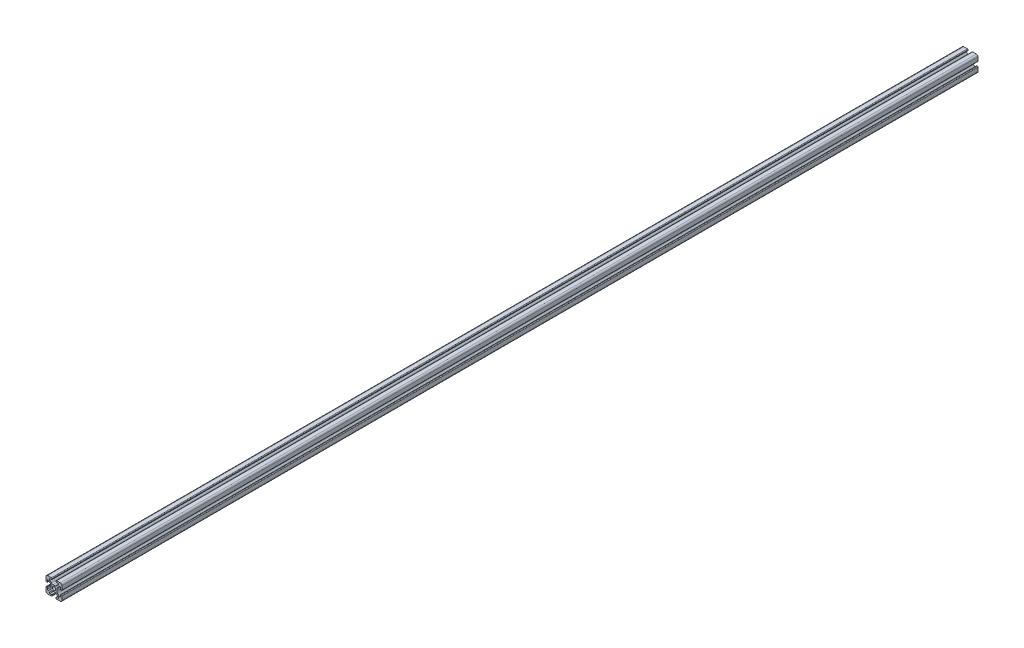
SolidWorks part; units mm, degrees
ref_plane "Front Plane" through (0, 0, 0) normal (0, 0, 1) x (1, 0, 0)
ref_plane "Top Plane" through (0, 0, 0) normal (0, 1, 0) x (1, 0, 0)
ref_plane "Right Plane" through (0, 0, 0) normal (1, 0, 0) x (0, 0, -1)
sketch "Sketch1" plane through (0, 0, 0) normal (0, 0, 1) x (1, 0, 0)
  line L0 (0, 10) -> (0, -10) construction
  line L1 (10, 0) -> (-10, 0) construction
  line L2 (-2.5, 10) -> (2.5, 10) construction
  line L3 (-5.75, 8.2) -> (5.75, 8.2) construction
  circle A0 centre (0, 0) radius 2.15 construction
  point P4 (0, 0)
  point P8 (0, 0)
  point P10 (0, 3.6)
  point P14 (0, 10)
  point P17 (0, 8.2)
  dimension "Thru Hole" = 4.3
  dimension "Height" = 20
  dimension "T Slot Depth" = 6.4
  dimension "T Slot Top Width" = 5
  dimension "T Slot Max Width" = 11.5
  dimension "Wall" = 1.8
sketch "Sketch2" plane through (0, 0, 0) normal (1, 0, 0) x (0, 0, -1)
  line L0 (575, 0) -> (-575, 0) construction
  point P4 (0, 0)
  dimension "D1" = 1150
sketch "Sketch3" plane through (0, 0, 0) normal (0, 0, 1) x (1, 0, 0)
  line L0 (3.2874, 10) -> (8, 10)
  line L1 (10, 8) -> (10, -8) construction
  line L2 (8, -10) -> (-8, -10) construction
  line L3 (-10, 10) -> (10, -10) construction
  line L4 (2.5, 9.2126) -> (2.5, 8.5048)
  line L5 (-5.75, 8.2) -> (5.75, 8.2) construction
  line L6 (2.8048, 8.2) -> (4.9118, 8.2)
  line L7 (5.5045, 6.7691) -> (3.2141, 4.4787)
  line L8 (1.0928, 3.6) -> (-1.0928, 3.6)
  line L9 (0, 10) -> (0, -10) construction
  line L10 (5.75, 8.2) -> (5.75, 0) construction
  line L11 (10, 0) -> (-10, 0) construction
  line L12 (0, 0) -> (0, 10) construction
  line L13 (-2.5, 9.2126) -> (-2.5, 8.5048)
  line L14 (-5.5045, 6.7691) -> (-3.2141, 4.4787)
  line L15 (-2.8048, 8.2) -> (-4.9118, 8.2)
  line L16 (-3.2874, 10) -> (-8, 10)
  line L17 (0, 0) -> (-10, 0) construction
  line L18 (-10, 3.2874) -> (-10, 8)
  line L19 (-8.2, 2.8048) -> (-8.2, 4.9118)
  line L20 (-6.7691, 5.5045) -> (-4.4787, 3.2141)
  line L21 (-9.2126, 2.5) -> (-8.5048, 2.5)
  line L22 (-3.6, -1.0928) -> (-3.6, 1.0928)
  line L23 (-6.7691, -5.5045) -> (-4.4787, -3.2141)
  line L24 (-8.2, -2.8048) -> (-8.2, -4.9118)
  line L25 (-9.2126, -2.5) -> (-8.5048, -2.5)
  line L26 (-10, -3.2874) -> (-10, -8)
  line L27 (9.2126, -2.5) -> (8.5048, -2.5)
  line L28 (8.2, -2.8048) -> (8.2, -4.9118)
  line L29 (6.7691, -5.5045) -> (4.4787, -3.2141)
  line L30 (3.6, -1.0928) -> (3.6, 1.0928)
  line L31 (9.2126, 2.5) -> (8.5048, 2.5)
  line L32 (6.7691, 5.5045) -> (4.4787, 3.2141)
  line L33 (8.2, 2.8048) -> (8.2, 4.9118)
  line L34 (10, 8) -> (10, 3.2874)
  line L35 (10, -3.2874) -> (10, -8)
  line L36 (3.2874, -10) -> (8, -10)
  line L37 (-3.2874, -10) -> (-8, -10)
  line L38 (-6.7691, -5.5045) -> (-4.4787, -3.2141)
  line L39 (-2.8048, -8.2) -> (-4.9118, -8.2)
  line L40 (-5.5045, -6.7691) -> (-3.2141, -4.4787)
  line L41 (-2.5, -9.2126) -> (-2.5, -8.5048)
  line L42 (1.0928, -3.6) -> (-1.0928, -3.6)
  line L43 (5.5045, -6.7691) -> (3.2141, -4.4787)
  line L44 (2.8048, -8.2) -> (4.9118, -8.2)
  line L45 (2.5, -9.2126) -> (2.5, -8.5048)
  arc A0 (4.9118, 8.2) -> (5.5045, 6.7691) centre (4.9118, 7.3618) cw
  arc A1 (3.2141, 4.4787) -> (1.0928, 3.6) centre (1.0928, 6.6) cw
  circle A2 centre (0, 0) radius 2.15 construction
  circle A3 centre (0, 0) radius 2.15
  arc A4 (3.2874, 10) -> (2.5, 9.2126) centre (3.2874, 9.2126) ccw
  arc A5 (2.5, 8.5048) -> (2.8048, 8.2) centre (2.8048, 8.5048) ccw
  arc A6 (-3.2874, 10) -> (-2.5, 9.2126) centre (-3.2874, 9.2126) cw
  arc A7 (-4.9118, 8.2) -> (-5.5045, 6.7691) centre (-4.9118, 7.3618) ccw
  arc A8 (-3.2141, 4.4787) -> (-1.0928, 3.6) centre (-1.0928, 6.6) ccw
  arc A9 (-2.5, 8.5048) -> (-2.8048, 8.2) centre (-2.8048, 8.5048) cw
  arc A10 (-8.5048, 2.5) -> (-8.2, 2.8048) centre (-8.5048, 2.8048) ccw
  arc A11 (-4.4787, 3.2141) -> (-3.6, 1.0928) centre (-6.6, 1.0928) cw
  arc A12 (-8.2, 4.9118) -> (-6.7691, 5.5045) centre (-7.3618, 4.9118) cw
  arc A13 (-10, 3.2874) -> (-9.2126, 2.5) centre (-9.2126, 3.2874) ccw
  arc A14 (-8.5048, -2.5) -> (-8.2, -2.8048) centre (-8.5048, -2.8048) cw
  arc A15 (-10, -3.2874) -> (-9.2126, -2.5) centre (-9.2126, -3.2874) cw
  arc A16 (-4.4787, -3.2141) -> (-3.6, -1.0928) centre (-6.6, -1.0928) ccw
  arc A17 (-8.2, -4.9118) -> (-6.7691, -5.5045) centre (-7.3618, -4.9118) ccw
  arc A26 (-8, -10) -> (-10, -8) centre (-8, -8) cw
  arc A27 (-8, 10) -> (-10, 8) centre (-8, 8) ccw
  arc A28 (8, 10) -> (10, 8) centre (8, 8) cw
  arc A29 (10, -8) -> (8, -10) centre (8, -8) cw
  arc A30 (8.2, -4.9118) -> (6.7691, -5.5045) centre (7.3618, -4.9118) cw
  arc A31 (4.4787, -3.2141) -> (3.6, -1.0928) centre (6.6, -1.0928) cw
  arc A32 (10, -3.2874) -> (9.2126, -2.5) centre (9.2126, -3.2874) ccw
  arc A33 (8.5048, -2.5) -> (8.2, -2.8048) centre (8.5048, -2.8048) ccw
  arc A34 (10, 3.2874) -> (9.2126, 2.5) centre (9.2126, 3.2874) cw
  arc A35 (8.2, 4.9118) -> (6.7691, 5.5045) centre (7.3618, 4.9118) ccw
  arc A36 (4.4787, 3.2141) -> (3.6, 1.0928) centre (6.6, 1.0928) ccw
  arc A37 (8.5048, 2.5) -> (8.2, 2.8048) centre (8.5048, 2.8048) cw
  arc A38 (-2.5, -8.5048) -> (-2.8048, -8.2) centre (-2.8048, -8.5048) ccw
  arc A39 (-3.2141, -4.4787) -> (-1.0928, -3.6) centre (-1.0928, -6.6) cw
  arc A40 (-4.9118, -8.2) -> (-5.5045, -6.7691) centre (-4.9118, -7.3618) cw
  arc A41 (-3.2874, -10) -> (-2.5, -9.2126) centre (-3.2874, -9.2126) ccw
  arc A42 (2.5, -8.5048) -> (2.8048, -8.2) centre (2.8048, -8.5048) cw
  arc A43 (3.2874, -10) -> (2.5, -9.2126) centre (3.2874, -9.2126) cw
  arc A44 (3.2141, -4.4787) -> (1.0928, -3.6) centre (1.0928, -6.6) ccw
  arc A45 (4.9118, -8.2) -> (5.5045, -6.7691) centre (4.9118, -7.3618) ccw
  point P36 (2.5, 10)
  point P39 (2.5, 8.2)
  point P49 (0, 3.6)
  point P77 (-3.6, 0)
  point P78 (-8.2, -2.5)
  point P79 (-10, -2.5)
  point P104 (-10, -10)
  point P110 (10, 10)
  point P114 (10, -2.5)
  point P115 (8.2, -2.5)
  point P116 (3.6, 0)
  point P141 (0, -3.6)
  dimension "D1" = 3
  dimension "D2" = 0.8382
  dimension "D4" = 0.7874
  dimension "D5" = 0.3048
  dimension "D6" = 2
  dimension "D3" = 45
extrude "Boss-Extrude1" add sketch "Sketch3" along normal up to vertex (575 mm away) and the other way up to vertex (575 mm away) contours A45 L44 A42 L45 A43 L36 A29 L35 A32 L27 A33 L28 A30 L29 A31 L30 A36 L32 A35 L33 A37 L31 A34 L34 A28 L0 A4 L4 A5 L6 A0 L7 A1 L8 A8 L14 A7 L15 A9 L13 A6 L16 A27 L18 A13 L21 A10 L19 A12 L20 A11 region at (5.6437, 9.7172, 0) up to point (0, 0, 575) other way up to point (0, 0, -575)
